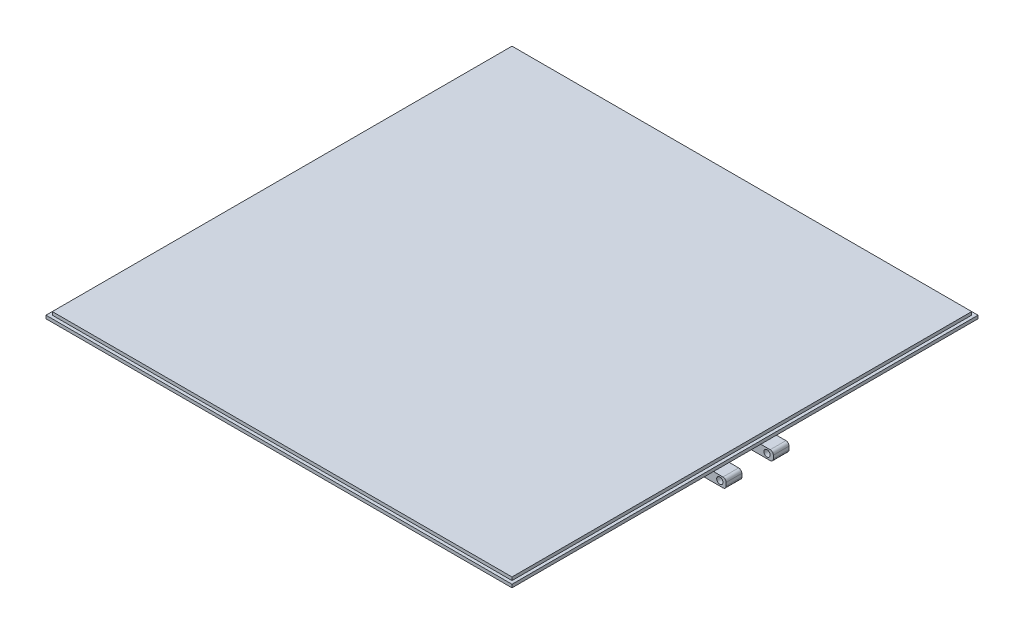
SolidWorks part; units mm, degrees
note: The reader was unsure of these and kept them because the rebuilt part matched: shared geometry of "Sketch6<2>".
material "A286 Iron Base Superalloy"
ref_plane "Front Plane" through (0, 0, 0) normal (0, 0, 1) x (1, 0, 0)
ref_plane "Top Plane" through (0, 0, 0) normal (0, 1, 0) x (1, 0, 0)
ref_plane "Right Plane" through (0, 0, 0) normal (1, 0, 0) x (0, 0, -1)
sketch "Sketch1" plane through (0, 0, 0) normal (0, 1, 0) x (1, 0, 0)
  circle A0 centre (0, 0) radius 10
  circle A2 centre (0, 0) radius 7.5
  dimension "D1" = 20
  dimension "D2" = 15
extrude "Boss-Extrude1" add sketch "Sketch1" along normal blind 25
thread "Thread1" pitch 0.3175 start angle 0, offset 0.5, length 6, pitch 0.3175, diameter 20
ref_plane "Plane1" through (10, -0.5, 0) normal (0, 0, 1) x (1, 0, 0)
sketch "Thread Profile1" plane through (10, -0.5, 0) normal (0, 0, 1) x (1, 0, 0)
  line L0 (0, 0) -> (0, 0.3175) construction
  line L11 (0, 0) -> (0, 0.2778)
  line L12 (0, 0.2778) -> (-0.1719, 0.1786)
  line L13 (-0.1719, 0.1786) -> (-0.1719, 0.0992)
  line L15 (-0.1719, 0.0992) -> (0, 0)
  line L17 (-0.1719, 0.1389) -> (0, 0.1389) construction
  point P2 (0, 0)
  dimension "Pitch" = 0.3175
  dimension "Profile_Angle" = 60
  dimension "Profile_Land" = 0.0794
  dimension "Profile_Height" = 0.1719
sketch "Sketch4" plane through (0, 25, 0) normal (0, 1, 0) x (1, 0, 0)
  line L0 (0, 0) -> (73, 0) construction
  line L1 (73, 0) -> (73, -73) construction
  line L3 (73, -73) -> (-73, -73)
  line L4 (73, -73) -> (73, 73)
  line L5 (73, 73) -> (-73, 73)
  line L6 (-73, -73) -> (-73, 73)
  dimension "D1" = 73
  dimension "D2" = 73
  dimension "D3" = 146
  dimension "D4" = 146
  dimension "D5" = 73
extrude "Boss-Extrude2" add sketch "Sketch4" along normal blind 2
sketch "Sketch5" plane through (0, 25, 0) normal (0, -1, 0) x (1, 0, 0)
  line L0 (-73, -73) -> (-73, 73) construction
  line L1 (-74, 74) -> (74, 74)
  line L2 (-74, 74) -> (-74, -74)
  line L3 (-74, -74) -> (74, -74)
  line L4 (74, 74) -> (74, -74)
  line L5 (73, -73) -> (-73, -73) construction
  dimension "D1" = 148
  dimension "D2" = 148
  dimension "D3" = 1
  dimension "D4" = 1
extrude "Boss-Extrude3" add sketch "Sketch5" against normal blind 1
sketch "Sketch6" plane through (0, 0, 0) normal (0, 0, 1) x (1, 0, 0)
  line L0 (74, 25) -> (-74, 25) construction
  line L1 (68, 25) -> (78, 25)
  line L2 (68, 25) -> (68, 22)
  line L3 (68, 22) -> (78, 22)
  line L4 (78, 25) -> (78, 22)
  line L5 (0, 0) -> (0, 25) construction
  line L6 (-10, 25) -> (10, 25) construction
  circle A0 centre (76, 23.5) radius 1
  dimension "D4" = 2
  dimension "D1" = 3
  dimension "D2" = 10
  dimension "D3" = 6
  dimension "D5" = 2
  dimension "D6" = 1.5
extrude "Boss-Extrude4" add sketch "Sketch6" along normal mid plane 5 from offset 7.5
extrude "Boss-Extrude5" add sketch "Sketch6<2>" along normal mid plane 5 from offset 7.5 offset against normal yes
sketch "Sketch6<2>" plane through (0, 0, 0) normal (0, 0, 1) x (1, 0, 0) same geometry as "Sketch6"
sketch "Sketch9" plane through (0, 25, 0) normal (0, -1, 0) x (1, 0, 0)
  circle A0 centre (0, 0) radius 18.9956
extrude "Cut-Extrude1" cut sketch "Sketch9" along normal through all
chamfer "Chamfer1" distance 3 angle 45 2 edges at (68, 25, -7.5) (68, 25, 7.5)
fillet "Fillet1" radius 1 4 edges at (78, 25, -7.5) (78, 22, -7.5) (78, 22, 7.5) (78, 25, 7.5)
